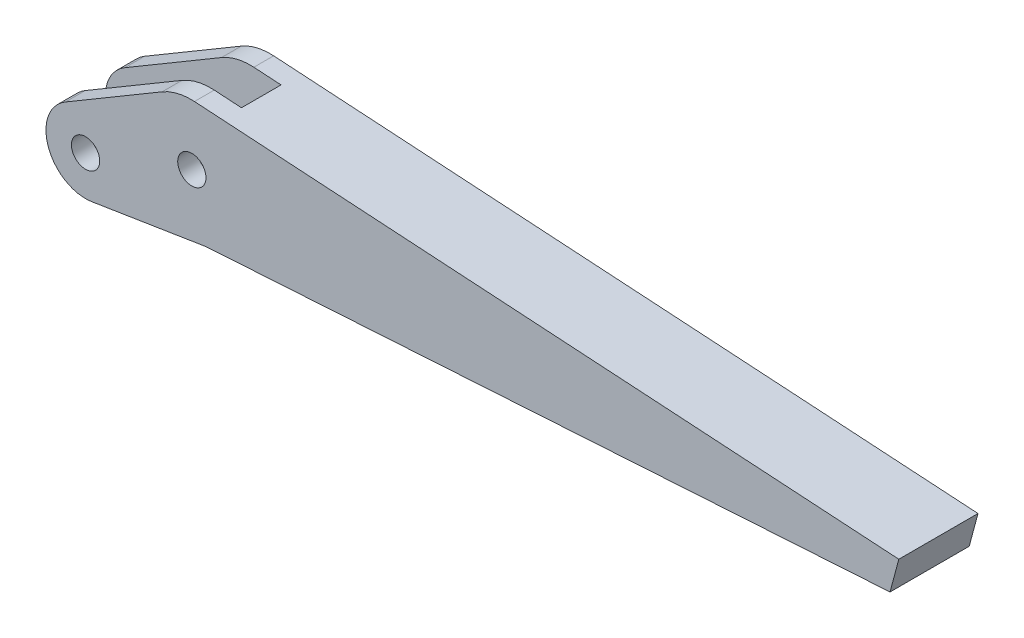
SolidWorks part; units mm, degrees
ref_plane "Front Plane" through (0, 0, 0) normal (0, 0, 1) x (1, 0, 0)
ref_plane "Top Plane" through (0, 0, 0) normal (0, 1, 0) x (1, 0, 0)
ref_plane "Right Plane" through (0, 0, 0) normal (1, 0, 0) x (0, 0, -1)
sketch "Sketch1" plane through (0, 0, 0) normal (0, 0, 1) x (1, 0, 0)
  line L0 (61.7218, -1.4733) -> (1.2642, -5.2676)
  line L1 (1.2642, -5.2676) -> (-8.8468, -6.8767)
  line L2 (-2.7378, 11.4079) -> (3.0838, -12.8496) construction
  line L3 (-11.1776, -0.407) -> (-1.3029, 5.4287)
  line L4 (-1.3029, 5.4287) -> (62.4983, 1.4245)
  line L5 (62.4983, 1.4245) -> (61.7218, -1.4733)
  line L6 (-64.0032, 0) -> (174.8266, 0) construction
  line L7 (-9.3969, -3.4202) -> (32.1602, 11.7054) construction
  line L8 (57.2784, -18.0563) -> (72.9137, 40.2955) construction
  arc A0 (-11.1776, -0.407) -> (-8.8468, -6.8767) centre (-9.3969, -3.4202) ccw
  circle A1 centre (0, 0) radius 1.25
  circle A2 centre (-9.3969, -3.4202) radius 1.25
  point P18 (62.11, -0.0244)
  dimension "D1" = 3.5
  dimension "D3" = 2.5
  dimension "D2" = 10
  dimension "D4" = 55
  dimension "D5" = 60
  dimension "D6" = 11
  dimension "D7" = 3
  dimension "D8" = 20
extrude "Boss-Extrude1" add sketch "Sketch1" along normal blind 7
ref_plane "Plane1" through (0.4275, -1.1746, 0) normal (-0.342, 0.9397, 0) x (0.9397, 0.342, 0)
sketch "Sketch2" plane through (0.4275, -1.1746, 0) normal (-0.342, 0.9397, 0) x (0.9397, 0.342, 0)
  line L0 (7.125, -3.5) -> (-34.8104, -3.5) construction
  line L1 (0.6324, 0) -> (-10.6427, 0) construction
  line L2 (0.6324, -7) -> (-10.6427, -7) construction
  line L3 (1.25, 5.4671) -> (1.25, -7) construction
  line L4 (4.25, -5.25) -> (-28.3424, -5.25)
  line L5 (4.25, -5.25) -> (4.25, -1.75)
  line L6 (4.25, -1.75) -> (-28.3424, -1.75)
  line L7 (-28.3424, -5.25) -> (-28.3424, -1.75)
  line L8 (4.25, -5.25) -> (-28.3424, -1.75) construction
  line L9 (4.25, -1.75) -> (-28.3424, -5.25) construction
  point P6 (-12.0462, -3.5)
  dimension "D1" = 3.5
  dimension "D2" = 3
extrude "Cut-Extrude1" cut sketch "Sketch2" against normal through all both and the other way through all
fillet "Fillet1" radius 5 4 edges at (1.2642, -5.2676, 6.125) (1.2642, -5.2676, 0.875) (-1.3029, 5.4287, 6.125) (-1.3029, 5.4287, 0.875)
